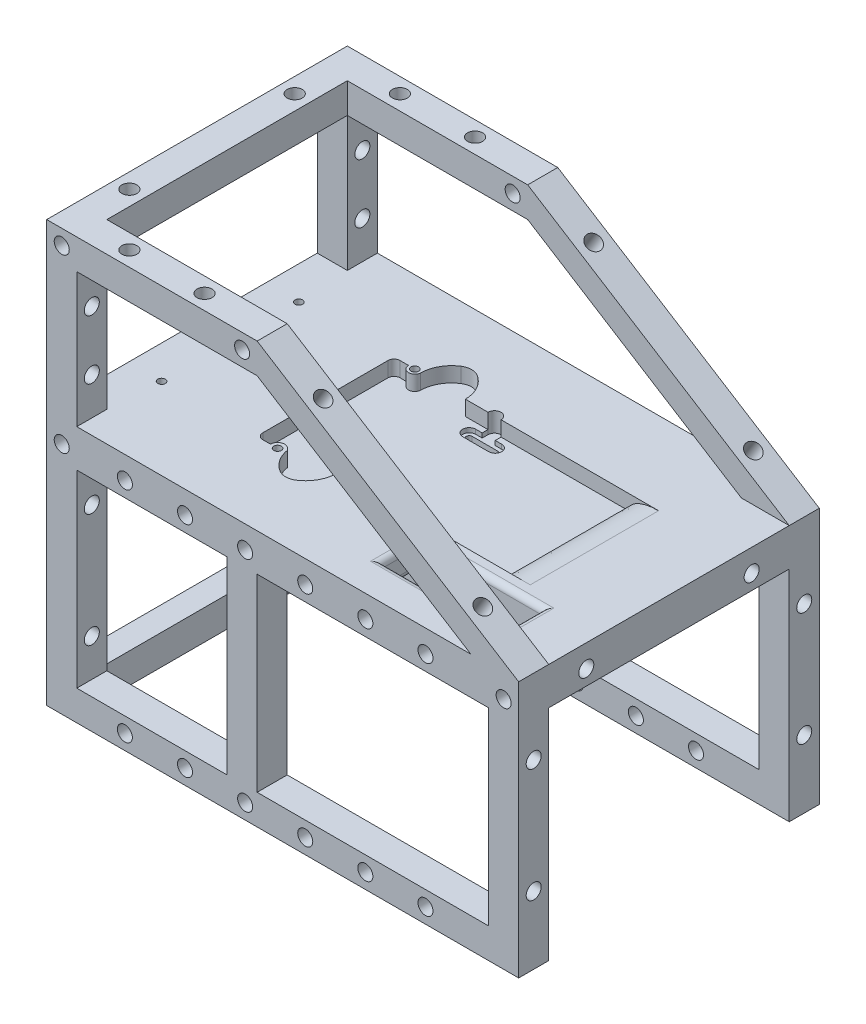
SolidWorks part; units mm, degrees
ref_plane "Front Plane" through (0, 0, 0) normal (0, 0, 1) x (1, 0, 0)
ref_plane "Top Plane" through (0, 0, 0) normal (0, 1, 0) x (1, 0, 0)
ref_plane "Right Plane" through (0, 0, 0) normal (1, 0, 0) x (0, 0, -1)
sketch "Sketch1" plane through (0, 0, 0) normal (0, 1, 0) x (1, 0, 0)
  line L0 (0, 0) -> (0, 50.8)
  line L1 (0, 50.8) -> (50.8, 50.8)
  line L4 (0, 50.8) -> (199.39, 50.8)
  line L5 (0, 50.8) -> (0, 38.1)
  line L8 (0, 50.8) -> (12.7, 50.8)
  line L9 (0, 50.8) -> (0, -76.2)
  line L13 (12.7, -12.7) -> (199.39, -12.7) construction
  line L14 (99.695, 34.925) -> (99.695, -76.2) construction
  line L18 (199.39, 50.8) -> (199.39, -76.2)
  line L19 (199.39, 50.8) -> (186.69, 50.8)
  line L20 (199.39, 50.8) -> (199.39, 38.1)
  line L22 (199.39, 50.8) -> (148.59, 50.8)
  line L23 (199.39, 0) -> (199.39, 50.8)
  line L24 (199.39, -25.4) -> (199.39, -76.2)
  line L25 (199.39, -76.2) -> (148.59, -76.2)
  line L27 (199.39, -76.2) -> (199.39, -63.5)
  line L28 (199.39, -76.2) -> (186.69, -76.2)
  line L29 (0, -76.2) -> (12.7, -76.2)
  line L30 (0, -76.2) -> (0, -63.5)
  line L31 (0, -76.2) -> (199.39, -76.2)
  line L34 (0, -76.2) -> (50.8, -76.2)
  line L35 (0, -25.4) -> (0, -76.2)
  line L36 (12.7, -12.7) -> (12.7, 38.1)
  line L37 (12.7, 38.1) -> (186.69, 38.1)
  line L38 (186.69, 38.1) -> (186.69, -63.5)
  line L39 (186.69, -63.5) -> (12.7, -63.5)
  line L40 (12.7, -63.5) -> (12.7, -12.7)
  point P19 (99.695, 50.8)
  point P22 (99.695, -76.2)
  point P32 (0, -12.7)
  dimension "D1" = 50.8
  dimension "D2" = 50.8
  dimension "D3" = 12.7
  dimension "D4" = 63.5
  dimension "D5" = 12.7
extrude "Boss-Extrude1" add sketch "Sketch1" along normal blind 12.7 contours L38 L39 L40 L36 L37 | L31 L18 L4 L9
sketch "Sketch2" plane through (0, 12.7, 0) normal (0, 1, 0) x (1, 0, 0)
  line L0 (12.7, 38.1) -> (186.69, 38.1) construction
  line L1 (0, 50.8) -> (12.7, 50.8)
  line L2 (0, 50.8) -> (0, 38.1)
  line L3 (0, 38.1) -> (12.7, 38.1)
  line L4 (12.7, 50.8) -> (12.7, 38.1)
  line L5 (199.39, 50.8) -> (186.69, 50.8)
  line L6 (199.39, 50.8) -> (199.39, 38.1)
  line L7 (199.39, 38.1) -> (186.69, 38.1)
  line L8 (186.69, 50.8) -> (186.69, 38.1)
  line L10 (199.39, -76.2) -> (186.69, -76.2)
  line L11 (199.39, -76.2) -> (199.39, -63.5)
  line L12 (199.39, -63.5) -> (186.69, -63.5)
  line L13 (186.69, -76.2) -> (186.69, -63.5)
  line L14 (0, -76.2) -> (12.7, -76.2)
  line L15 (0, -76.2) -> (0, -63.5)
  line L16 (0, -63.5) -> (12.7, -63.5)
  line L17 (12.7, -76.2) -> (12.7, -63.5)
extrude "Boss-Extrude2" add sketch "Sketch2" along normal blind 95.675
sketch "Sketch3" plane through (0, 108.375, 0) normal (0, 1, 0) x (1, 0, 0)
  line L0 (199.39, -76.2) -> (199.39, -63.5) construction
  line L1 (0, 50.8) -> (199.39, 50.8)
  line L2 (0, 50.8) -> (0, -76.2)
  line L3 (0, -76.2) -> (199.39, -76.2)
  line L4 (199.39, 50.8) -> (199.39, -76.2)
  line L5 (186.69, -76.2) -> (199.39, -76.2) construction
  line L7 (12.7, 38.1) -> (186.69, 38.1)
  line L8 (12.7, 38.1) -> (12.7, -63.5)
  line L9 (12.7, -63.5) -> (186.69, -63.5)
  line L10 (186.69, 38.1) -> (186.69, -63.5)
extrude "Boss-Extrude4" add sketch "Sketch3" against normal blind 15.875
sketch "Sketch4" plane through (0, 0, 0) normal (0, -1, 0) x (1, 0, 0)
  line L0 (0, -50.8) -> (199.39, -50.8) construction
  line L1 (0, 76.2) -> (12.7, 76.2)
  line L2 (0, 76.2) -> (0, 63.5)
  line L3 (0, 63.5) -> (12.7, 63.5)
  line L4 (12.7, 76.2) -> (12.7, 63.5)
  line L5 (0, -50.8) -> (12.7, -50.8)
  line L6 (0, -50.8) -> (0, -38.1)
  line L7 (0, -38.1) -> (12.7, -38.1)
  line L8 (12.7, -50.8) -> (12.7, -38.1)
  line L9 (76.2, -50.8) -> (88.9, -50.8)
  line L10 (76.2, -50.8) -> (76.2, -38.1)
  line L11 (76.2, -38.1) -> (88.9, -38.1)
  line L12 (88.9, -50.8) -> (88.9, -38.1)
  line L13 (12.7, -38.1) -> (186.69, -38.1) construction
  line L14 (186.69, 63.5) -> (12.7, 63.5) construction
  line L15 (76.2, 63.5) -> (88.9, 63.5)
  line L16 (76.2, 63.5) -> (76.2, 76.2)
  line L17 (76.2, 76.2) -> (88.9, 76.2)
  line L18 (88.9, 63.5) -> (88.9, 76.2)
  line L19 (0, 76.2) -> (199.39, 76.2) construction
  dimension "D1" = 12.7
  dimension "D2" = 88.9
  dimension "D3" = 88.9
extrude "Boss-Extrude5" add sketch "Sketch4" against normal blind 177.8
sketch "Sketch5" plane through (0, 177.8, 0) normal (0, 1, 0) x (1, 0, 0)
  line L0 (88.9, 50.8) -> (0, 50.8)
  line L1 (0, 50.8) -> (0, -76.2)
  line L2 (0, -76.2) -> (88.9, -76.2)
  line L3 (88.9, -76.2) -> (88.9, -63.5)
  line L4 (88.9, -63.5) -> (12.7, -63.5)
  line L5 (12.7, -63.5) -> (12.7, 38.1)
  line L6 (12.7, 38.1) -> (88.9, 38.1)
  line L7 (88.9, 38.1) -> (88.9, 50.8)
extrude "Boss-Extrude6" add sketch "Sketch5" against normal blind 12.7
sketch "Sketch7" plane through (199.39, 0, 0) normal (1, 0, 0) x (0, 0, -1)
  line L5 (50.8, 0) -> (-76.2, 0) construction
  line L6 (-63.5, 12.7) -> (38.1, 12.7)
  line L7 (-63.5, 12.7) -> (-63.5, 0)
  line L8 (-63.5, 0) -> (38.1, 0)
  line L9 (38.1, 12.7) -> (38.1, 0)
extrude "Cut-Extrude1" cut sketch "Sketch7" against normal blind 15.875
sketch "Sketch8" plane through (12.7, 0, 0) normal (1, 0, 0) x (0, 0, -1)
  line L5 (50.8, 0) -> (38.1, 0) construction
  line L6 (-63.5, 12.7) -> (38.1, 12.7)
  line L7 (-63.5, 12.7) -> (-63.5, 0)
  line L8 (-63.5, 0) -> (38.1, 0)
  line L9 (38.1, 12.7) -> (38.1, 0)
extrude "Cut-Extrude2" cut sketch "Sketch8" against normal blind 2.54
sketch "Sketch9" plane through (0, 0, 76.2) normal (0, 0, 1) x (1, 0, 0)
  line L0 (12.7, 12.7) -> (76.2, 12.7) construction
  line L1 (0, 177.8) -> (0, 0) construction
  line L2 (12.7, 92.5) -> (76.2, 92.5) construction
  circle A0 centre (33.02, 98.85) radius 3.175
  circle A1 centre (58.42, 98.85) radius 3.175
  circle A2 centre (83.82, 98.85) radius 3.175
  circle A3 centre (109.22, 98.85) radius 3.175
  circle A4 centre (134.62, 98.85) radius 3.175
  circle A5 centre (160.02, 98.85) radius 3.175
  circle A6 centre (33.02, 6.35) radius 3.175
  circle A7 centre (58.42, 6.35) radius 3.175
  circle A8 centre (83.82, 6.35) radius 3.175
  circle A9 centre (109.22, 6.35) radius 3.175
  circle A10 centre (134.62, 6.35) radius 3.175
  circle A11 centre (160.02, 6.35) radius 3.175
  dimension "D2" = 6.35
  dimension "D6" = 6.35
  dimension "D1" = 6.35
  dimension "D4" = 33.02
  dimension "D5" = 6.35
  dimension "D3" = 6
  dimension "D7" = 6
extrude "Cut-Extrude3" cut sketch "Sketch9" against normal through all
sketch "Sketch24" plane through (0, 0, 63.5) normal (0, 0, -1) x (-1, 0, 0)
  line L0 (0, 177.8) -> (0, 0) construction
  line L2 (-199.39, 108.375) -> (0, 108.375)
  line L3 (-199.39, 108.375) -> (-199.39, 96.945)
  line L4 (-199.39, 96.945) -> (0, 96.945)
  line L5 (0, 108.375) -> (0, 96.945)
  dimension "D1" = 11.43
extrude "Boss-Extrude8" add sketch "Sketch24" along normal up to surface (101.6 mm away) up to face at (156.845, 98.85, -38.1)
sketch "Sketch10" plane through (0, 0, 76.2) normal (0, 0, 1) x (1, 0, 0)
  line L0 (88.9, 177.8) -> (88.9, 108.375) construction
  line L1 (12.7, 92.5) -> (76.2, 92.5) construction
  line L2 (0, 177.8) -> (0, 0) construction
  line L3 (88.9, 177.8) -> (0, 177.8) construction
  line L4 (199.39, 108.375) -> (199.39, 0) construction
  line L7 (88.9, 92.5) -> (186.69, 92.5) construction
  circle A1 centre (6.35, 98.85) radius 3.175
  circle A2 centre (6.35, 171.45) radius 3.175
  circle A4 centre (82.55, 171.45) radius 3.175
  circle A6 centre (193.04, 98.85) radius 3.175
  dimension "D3" = 6.35
  dimension "D4" = 6.35
  dimension "D5" = 6.35
  dimension "D7" = 6.35
  dimension "D8" = 6.35
  dimension "D10" = 6.35
  dimension "D2" = 6.35
  dimension "D6" = 6.35
  dimension "0." = 6.35
extrude "Cut-Extrude4" cut sketch "Sketch10" against normal blind 15.875
sketch "Sketch11" plane through (0, 0, -50.8) normal (0, 0, -1) x (-1, 0, 0)
  line L0 (-88.9, 177.8) -> (-88.9, 108.375) construction
  line L1 (-199.39, 108.375) -> (-199.39, 0) construction
  line L2 (0, 177.8) -> (0, 0) construction
  line L5 (0, 177.8) -> (-88.9, 177.8) construction
  line L6 (-76.2, 92.5) -> (-12.7, 92.5) construction
  line L7 (-186.69, 92.5) -> (-88.9, 92.5) construction
  circle A3 centre (-6.35, 98.85) radius 3.175
  circle A4 centre (-6.35, 171.45) radius 3.175
  circle A5 centre (-82.55, 171.45) radius 3.175
  circle A6 centre (-193.04, 98.85) radius 3.175
  dimension "D2" = 6.35
  dimension "D3" = 6.35
  dimension "D5" = 6.35
  dimension "D7" = 6.35
  dimension "D8" = 6.35
  dimension "D1" = 6.35
  dimension "D4" = 6.35
  dimension "D6" = 6.35
  dimension "0" = 6.35
extrude "Cut-Extrude5" cut sketch "Sketch11" against normal blind 15.875
sketch "Sketch12" plane through (0, 0, 0) normal (-1, 0, 0) x (0, 0, 1)
  line L0 (-38.1, 92.5) -> (-38.1, 12.7) construction
  line L1 (-38.1, 12.7) -> (63.5, 12.7) construction
  line L2 (-38.1, 92.5) -> (63.5, 92.5) construction
  line L3 (-38.1, 165.1) -> (63.5, 165.1) construction
  line L4 (-38.1, 108.375) -> (63.5, 108.375) construction
  line L5 (12.7, 177.8) -> (12.7, 0) construction
  line L6 (76.2, 177.8) -> (-50.8, 177.8) construction
  line L7 (-50.8, 0) -> (76.2, 0) construction
  line L8 (-44.45, 76.625) -> (-44.45, 28.575) construction
  line L9 (-44.45, 149.225) -> (-44.45, 124.25) construction
  line L10 (-38.1, 165.1) -> (-38.1, 108.375) construction
  circle A0 centre (-44.45, 28.575) radius 3.175
  circle A1 centre (-44.45, 76.625) radius 3.175
  circle A2 centre (-44.45, 124.25) radius 3.175
  circle A3 centre (-44.45, 149.225) radius 3.175
  circle A4 centre (69.85, 149.225) radius 3.175
  circle A5 centre (69.85, 124.25) radius 3.175
  circle A6 centre (69.85, 76.625) radius 3.175
  circle A7 centre (69.85, 28.575) radius 3.175
  dimension "D2" = 6.35
  dimension "D4" = 6.35
  dimension "D6" = 6.35
  dimension "D7" = 6.35
  dimension "D1" = 6.35
  dimension "D3" = 15.875
  dimension "D5" = 15.875
  dimension "D8" = 15.875
  dimension "D9" = 15.875
  dimension "D10" = 6.35
extrude "Cut-Extrude6" cut sketch "Sketch12" against normal blind 15.875
sketch "Sketch15" plane through (0, 0, 0) normal (0, -1, 0) x (1, 0, 0)
  line L0 (10.16, -38.1) -> (199.39, -38.1) construction
  line L1 (199.39, -50.8) -> (199.39, -38.1) construction
  line L3 (0, 76.2) -> (199.39, 76.2) construction
  line L7 (0, -50.8) -> (0, 76.2) construction
  line L8 (0, 12.7) -> (199.39, 12.7) construction
  line L9 (199.39, 63.5) -> (199.39, -38.1) construction
  line L13 (199.39, 63.5) -> (199.39, 76.2) construction
  circle A10 centre (6.35, 69.85) radius 3.175
  circle A11 centre (193.04, 69.85) radius 3.175
  circle A12 centre (6.35, -44.45) radius 3.175
  circle A13 centre (193.04, -44.45) radius 3.175
  dimension "D4" = 6.35
  dimension "D6" = 6.35
  dimension "D7" = 6.35
  dimension "D9" = 0
  dimension "D12" = 6.35
  dimension "D13" = 6.35
  dimension "D2" = 6.35
  dimension "D3" = 6.35
  dimension "D5" = 6.35
  dimension "D8" = 0
  dimension "D10" = 6.35
  dimension "D14" = 6.35
extrude "Cut-Extrude7" cut sketch "Sketch15" against normal blind 15.875
sketch "Sketch16" plane through (0, 177.8, 0) normal (0, 1, 0) x (1, 0, 0)
  line L0 (12.7, 50.8) -> (12.7, 38.1) construction
  line L1 (12.7, 38.1) -> (0, 38.1) construction
  line L2 (76.2, 50.8) -> (76.2, 38.1) construction
  line L3 (0, 50.8) -> (88.9, 50.8) construction
  line L4 (12.7, -63.5) -> (12.7, 38.1) construction
  line L5 (0, -12.7) -> (199.39, -12.7) construction
  line L6 (0, -76.2) -> (0, 50.8) construction
  line L7 (199.39, -76.2) -> (199.39, 50.8) construction
  line L8 (76.2, -76.2) -> (76.2, -63.5) construction
  line L9 (12.7, -63.5) -> (0, -63.5) construction
  line L10 (12.7, -76.2) -> (12.7, -63.5) construction
  line L11 (12.7, -63.5) -> (88.9, -63.5) construction
  circle A0 centre (28.575, 44.45) radius 3.175
  circle A1 centre (60.325, 44.45) radius 3.175
  circle A2 centre (6.35, 22.225) radius 3.175
  circle A3 centre (6.35, -47.625) radius 3.175
  circle A4 centre (60.325, -69.85) radius 3.175
  circle A5 centre (28.575, -69.85) radius 3.175
  dimension "D2" = 6.35
  dimension "D4" = 6.35
  dimension "D5" = 15.875
  dimension "D6" = 6.35
  dimension "D1" = 6.35
  dimension "D3" = 15.875
  dimension "D7" = 15.875
  dimension "D8" = 6.35
  dimension "D9" = 6.35
extrude "Cut-Extrude8" cut sketch "Sketch16" against normal blind 15.875
sketch "Sketch20" plane through (199.39, 0, 0) normal (1, 0, 0) x (0, 0, -1)
  line L0 (-63.5, 92.5) -> (-63.5, 0) construction
  line L1 (38.1, 12.7) -> (-63.5, 12.7) construction
  line L2 (-63.5, 92.5) -> (38.1, 92.5) construction
  line L3 (-76.2, 108.375) -> (-76.2, 0) construction
  line L4 (-63.5, 177.8) -> (-63.5, 108.375) construction
  line L5 (-12.7, 0) -> (-12.7, 177.8) construction
  line L6 (-63.5, 0) -> (38.1, 0) construction
  line L7 (-63.5, 177.8) -> (38.1, 177.8) construction
  circle A0 centre (-69.85, 28.575) radius 3.175
  circle A1 centre (-69.85, 76.625) radius 3.175
  circle A2 centre (-47.625, 98.85) radius 3.175
  circle A3 centre (22.225, 98.85) radius 3.175
  circle A4 centre (44.45, 76.625) radius 3.175
  circle A5 centre (44.45, 28.575) radius 3.175
  dimension "D2" = 6.35
  dimension "D3" = 6.35
  dimension "D5" = 6.35
  dimension "D1" = 6.35
  dimension "0.625" = 15.875
  dimension "D4" = 15.875
  dimension "D6" = 6.35
  dimension "D7" = 15.875
  dimension "D8" = 6.35
extrude "Cut-Extrude11" cut sketch "Sketch20" against normal blind 15.875
sketch "Sketch25" plane through (0, 108.375, 0) normal (0, 1, 0) x (1, 0, 0)
  line L0 (0, 50.8) -> (88.9, 50.8) construction
  line L1 (14.023, -41.7) -> (63.023, -41.7)
  line L2 (14.023, -41.7) -> (14.023, 16.3)
  line L3 (14.023, 16.3) -> (63.023, 16.3)
  line L4 (63.023, -41.7) -> (63.023, 16.3)
  line L5 (14.023, -41.7) -> (63.023, 16.3) construction
  line L6 (14.023, 16.3) -> (63.023, -41.7) construction
  line L7 (0, -76.2) -> (0, 50.8) construction
  line L8 (38.523, -12.7) -> (38.523, 16.3) construction
  line L9 (38.523, -12.7) -> (63.023, -12.7)
  circle A0 centre (63.023, 16.3) radius 1.6
  circle A1 centre (63.023, -41.7) radius 1.6
  circle A2 centre (14.023, -41.7) radius 1.6
  circle A3 centre (14.023, 16.3) radius 1.6
  point P0 (38.523, -12.7)
  dimension "D4" = 38.523
  dimension "D1" = 63.5
  dimension "D2" = 49
  dimension "D3" = 58
extrude "Cut-Extrude12" cut sketch "Sketch25" against normal up to surface (11.43 mm away) contours A2 | A1 | A0 | A3 up to face at (116.5578, 96.945, 12.7)
sketch "Sketch26" plane through (0, 108.375, 0) normal (0, 1, 0) x (1, 0, 0)
  line L0 (63.023, -41.7) -> (63.023, -63.5) construction
  line L5 (12.7, -63.5) -> (88.9, -63.5) construction
  line L6 (126.523, -44.345) -> (177.323, -44.345)
  line L7 (126.523, -44.345) -> (126.523, -60.855)
  line L8 (126.523, -60.855) -> (177.323, -60.855)
  line L9 (177.323, -44.345) -> (177.323, -60.855)
  line L10 (126.523, -44.345) -> (177.323, -60.855) construction
  line L11 (126.523, -60.855) -> (177.323, -44.345) construction
  point P0 (151.923, -52.6)
  point P10 (63.023, -52.6)
  dimension "D1" = 0
  dimension "D2" = 16.51
  dimension "D3" = 50.8
  dimension "D4" = 88.9
extrude "Cut-Extrude13" cut sketch "Sketch26" against normal through all
fillet "Fillet2" radius 2.54 5 edges at (126.523, 96.945, 52.6) (126.523, 108.375, 52.6) (177.323, 108.375, 52.6) (151.923, 108.375, 60.855) (151.923, 108.375, 44.345)
sketch "Sketch28" plane through (12.7, 0, 0) normal (1, 0, 0) x (0, 0, -1)
  line L1 (-63.5, 96.945) -> (38.1, 96.945)
  line L2 (-63.5, 96.945) -> (-63.5, 92.5)
  line L3 (-63.5, 92.5) -> (38.1, 92.5)
  line L4 (38.1, 96.945) -> (38.1, 92.5)
extrude "Cut-Extrude14" cut sketch "Sketch28" against normal blind 6.35
sketch "Sketch29" plane through (0, 0, 76.2) normal (0, 0, 1) x (1, 0, 0)
  line L1 (76.2, 165.1) -> (88.9, 165.1)
  line L2 (76.2, 165.1) -> (76.2, 108.375)
  line L3 (76.2, 108.375) -> (88.9, 108.375)
  line L4 (88.9, 165.1) -> (88.9, 108.375)
extrude "Cut-Extrude15" cut sketch "Sketch29" against normal through all
sketch "Sketch30" plane through (0, 0, 76.2) normal (0, 0, 1) x (1, 0, 0)
  line L0 (88.9, 177.8) -> (199.39, 108.375)
  line L1 (199.39, 108.375) -> (199.39, 0) construction
  line L2 (12.7, 108.375) -> (199.39, 108.375) construction
  line L3 (88.9, 165.1) -> (179.1779, 108.375)
  line L4 (179.1779, 108.375) -> (199.39, 108.375)
  line L5 (88.9, 177.8) -> (88.9, 165.1)
extrude "Boss-Extrude9" add sketch "Sketch30" against normal up to surface (12.7 mm away) contours L3 L4 L0 L5 up to face at (85.725, 171.45, 63.5)
sketch "Sketch31" plane through (0, 0, -50.8) normal (0, 0, -1) x (-1, 0, 0)
  line L0 (-88.9, 177.8) -> (-88.9, 165.1)
  line L1 (-88.9, 177.8) -> (-199.39, 108.375)
  line L2 (-88.9, 165.1) -> (-179.1779, 108.375)
  line L3 (-179.1779, 108.375) -> (-199.39, 108.375)
extrude "Boss-Extrude10" add sketch "Sketch31" against normal up to surface (12.7 mm away) up to face at (79.375, 171.45, -38.1)
sketch "Sketch32" plane through (105.2595, 167.5207, 0) normal (0.532, 0.8467, 0) x (0.8467, -0.532, 0)
  line L0 (-19.3209, 50.8) -> (111.17, 50.8) construction
  line L1 (-19.3209, 50.8) -> (-19.3209, 38.1) construction
  line L3 (111.17, 38.1) -> (111.17, 50.8) construction
  line L4 (111.17, -12.7) -> (-94.5948, -12.7) construction
  line L5 (111.17, -63.5) -> (111.17, 38.1) construction
  line L6 (-94.5948, -76.2) -> (-94.5948, 50.8) construction
  circle A0 centre (6.0791, 44.45) radius 3.175
  circle A1 centre (85.77, 44.45) radius 3.175
  circle A2 centre (85.77, -69.85) radius 3.175
  circle A3 centre (6.0791, -69.85) radius 3.175
  dimension "D1" = 6.35
  dimension "D2" = 6.35
  dimension "D3" = 6.35
  dimension "D4" = 6.35
  dimension "D5" = 25.4
  dimension "D6" = 25.4
extrude "Cut-Extrude16" cut sketch "Sketch32" against normal blind 12.7
sketch "Sketch34" plane through (0, 108.375, 0) normal (0, 1, 0) x (1, 0, 0)
  line L0 (63.023, 16.3) -> (63.023, -41.7) construction
  line L1 (153.663, -38.3) -> (65.663, -38.3)
  line L5 (153.663, 15.95) -> (153.663, -38.3)
  line L6 (65.663, -38.3) -> (65.663, 15.95)
  line L7 (65.663, 15.95) -> (153.663, 15.95)
  dimension "D1" = 88
  dimension "D2" = 5.28
  dimension "D3" = 54.25
extrude "Cut-Extrude18" cut sketch "Sketch34" against normal blind 6.35
sketch "Sketch35" plane through (0, 108.375, 0) normal (0, 1, 0) x (1, 0, 0)
  line L0 (65.663, 15.95) -> (84.713, 15.95)
  line L1 (153.663, 15.95) -> (65.663, 15.95) construction
  line L2 (65.663, -11.175) -> (153.663, -11.175) construction
  line L3 (65.663, -38.3) -> (84.713, -38.3)
  line L4 (65.663, -38.3) -> (153.663, -38.3) construction
  line L5 (75.188, 15.95) -> (75.188, 28.65) construction
  arc A0 (65.663, 15.95) -> (71.7688, 27.0976) centre (78.8922, 15.95) cw
  arc A2 (84.713, 15.95) -> (78.6072, 27.0976) centre (71.4838, 15.95) ccw
  arc A3 (78.6072, 27.0976) -> (71.7688, 27.0976) centre (75.188, 21.7467) ccw
  arc A4 (78.6072, -49.4476) -> (71.7688, -49.4476) centre (75.188, -44.0967) cw
  arc A5 (84.713, -38.3) -> (78.6072, -49.4476) centre (71.4838, -38.3) cw
  arc A6 (65.663, -38.3) -> (71.7688, -49.4476) centre (78.8922, -38.3) ccw
  dimension "D4" = 6.35
  dimension "D1" = 19.05
  dimension "D2" = 12.7
  dimension "D3" = 0
extrude "Cut-Extrude19" cut sketch "Sketch35" against normal blind 6.35
fillet "Fillet3" radius 12.7 1 edges at (153.663, 108.375, 11.175) second distance 6.35 first distance on face at (90.883, 108.375, 11.175)
ref_plane "Plane1" through (0, 115.8745, 0) normal (0, 1, 0) x (1, 0, 0)
sketch "Sketch37" plane through (0, 108.375, 0) normal (0, 1, 0) x (1, 0, 0)
  line L0 (65.663, -38.3) -> (97.033, -38.3)
  line L1 (84.713, -38.3) -> (153.663, -38.3) construction
  line L2 (97.033, -38.3) -> (97.033, -35.25)
  dimension "D1" = 31.37
  dimension "D2" = 3.05
sketch "Sketch38" plane through (0, 108.375, 0) normal (0, 1, 0) x (1, 0, 0)
  line L0 (89.533, -35.25) -> (104.533, -35.25)
  line L1 (89.533, -35.25) -> (89.533, -30.25)
  line L2 (89.533, -30.25) -> (104.533, -30.25)
  line L3 (104.533, -30.25) -> (104.533, -35.25)
  line L4 (91.533, -32) -> (102.533, -32)
  line L5 (91.533, -34.5) -> (102.533, -34.5)
  line L9 (91.533, 12) -> (102.533, 12)
  line L10 (91.533, 9.5) -> (102.533, 9.5)
  line L11 (91.533, -33.25) -> (91.533, 10.75) construction
  arc A0 (91.533, -32) -> (91.533, -34.5) centre (91.533, -33.25) ccw
  arc A1 (102.533, -34.5) -> (102.533, -32) centre (102.533, -33.25) ccw
  arc A2 (102.533, 12) -> (102.533, 9.5) centre (102.533, 10.75) cw
  arc A3 (91.533, 9.5) -> (91.533, 12) centre (91.533, 10.75) cw
  point P4 (97.033, -35.25)
  dimension "D3" = 2
  dimension "2.5mm" = 2.5
  dimension "D5" = 2.5
  dimension "D1" = 15
  dimension "D2" = 5
  dimension "D4" = 2
  dimension "D6" = 2
  dimension "D7" = 2
  dimension "D8" = 44
extrude "Cut-Extrude20" cut sketch "Sketch38" against normal through all and the other way through all contours L4 A1 L5 A0 | A3 L9 A2 L10
sketch "Sketch41" plane through (0, 102.025, 0) normal (0, 1, 0) x (1, 0, 0)
  line L2 (91.533, 10.75) -> (102.533, 10.75) construction
  line L3 (91.533, -30.5) -> (102.533, -30.5)
  line L6 (91.533, -36) -> (102.533, -36)
  line L7 (91.533, 13.5) -> (102.533, 13.5)
  line L9 (91.533, 8) -> (102.533, 8)
  arc A4 (102.533, 13.5) -> (102.533, 8) centre (102.533, 10.75) cw
  arc A5 (91.533, 8) -> (91.533, 13.5) centre (91.533, 10.75) cw
  arc A7 (91.533, -30.5) -> (91.533, -36) centre (91.533, -33.25) ccw
  arc A8 (102.533, -36) -> (102.533, -30.5) centre (102.533, -33.25) ccw
  arc A9 (91.533, 12) -> (91.533, 9.5) centre (91.533, 10.75) ccw construction
  point P17 (90.283, 10.75)
  dimension "D1" = 5.5
  dimension "D2" = 5.5
  dimension "D3" = 0
extrude "Cut-Extrude21" cut sketch "Sketch41" against normal blind 1.878
sketch "Sketch42" plane through (0, 108.375, 0) normal (0, 1, 0) x (1, 0, 0)
  line L0 (65.663, -11.175) -> (166.363, -11.175) construction
  line L1 (65.663, 15.95) -> (65.663, -38.3) construction
  line L2 (84.713, -38.3) -> (166.363, -38.3) construction
  line L3 (94.283, -38.3) -> (94.283, -36)
  line L4 (91.533, -36) -> (102.533, -36) construction
  line L5 (94.283, -36) -> (99.783, -36)
  line L6 (91.533, -36) -> (102.533, -36) construction
  line L7 (99.783, -36) -> (99.783, -38.3)
  line L8 (166.363, 15.95) -> (166.363, -38.3) construction
  line L9 (99.783, 13.65) -> (99.783, 15.95)
  line L11 (94.283, 15.95) -> (94.283, 13.65)
  line L12 (94.283, 13.65) -> (94.283, 13.5)
  line L13 (102.533, 13.5) -> (91.533, 13.5) construction
  line L14 (94.283, 13.5) -> (99.783, 13.5)
  line L15 (99.783, 13.5) -> (99.783, 13.65)
  arc A0 (94.283, -38.3) -> (99.783, -38.3) centre (97.033, -38.3) ccw
  arc A1 (94.283, 15.95) -> (99.783, 15.95) centre (97.033, 15.95) cw
  dimension "D1" = 5.5
  dimension "D2" = 0
extrude "Cut-Extrude22" cut sketch "Sketch42" against normal up to surface (8.228 mm away) up to face at (97.033, 100.147, -10.75)
sketch "Sketch43" plane through (0, 96.945, 0) normal (0, -1, 0) x (1, 0, 0)
  circle A0 centre (63.023, 41.7) radius 2.54
  circle A1 centre (63.023, -16.3) radius 2.54
  circle A2 centre (14.023, -16.3) radius 2.54
  circle A3 centre (14.023, 41.7) radius 2.54
  dimension "D1" = 5.08
  dimension "D2" = 5.08
  dimension "D3" = 5.08
  dimension "D4" = 5.08
extrude "Cut-Extrude23" cut sketch "Sketch43" against normal blind 8.255
sketch "Sketch44" plane through (0, 0, 76.2) normal (0, 0, 1) x (1, 0, 0)
  line L0 (0, 177.8) -> (138.1279, 177.8) construction
  line L1 (88.9, 177.8) -> (199.39, 108.375) construction
  line L2 (199.39, 108.375) -> (151.2695, 108.375) construction
  dimension "D1" = 32.143
  dimension "D2" = 32.143
sketch "Sketch45" plane through (0, 108.375, 0) normal (0, 1, 0) x (1, 0, 0)
  line L0 (60.0229, -41.7) -> (60.0231, -41.6651)
  line L2 (65.663, 15.95) -> (65.663, -38.3)
  line L3 (65.663, 15.95) -> (65.663, -38.3)
  line L4 (60.3599, 16.3) -> (56.773, 16.3)
  line L5 (65.663, -38.3) -> (65.9075, -40.2748)
  line L6 (65.9075, -40.2748) -> (65.663, -40.2748)
  line L7 (54.233, 13.76) -> (54.233, -39.1447)
  line L8 (56.7883, -41.6846) -> (60.0231, -41.6651)
  line L9 (63.023, 16.3) -> (62.8476, 13.6427) construction
  arc A0 (60.3599, 16.3) -> (65.663, 15.95) centre (63.023, 16.3) ccw
  arc A1 (60.0231, -41.6651) -> (60.0229, -41.7) centre (63.023, -41.7) ccw
  arc A2 (65.663, -40.2748) -> (60.0229, -41.7) centre (63.023, -41.7) ccw
  arc A3 (54.233, -39.1447) -> (56.7883, -41.6846) centre (56.773, -39.1447) ccw
  arc A4 (56.773, 16.3) -> (54.233, 13.76) centre (56.773, 13.76) ccw
  arc M5 (71.7688, -49.4476) -> (65.663, -38.3) centre (78.8922, -38.3) cw
  line M6 (65.663, -38.3) -> (65.663, 15.95)
  dimension "D2" = 2.54
  dimension "D1" = 11.43
  dimension "D3" = 2.6631
extrude "Cut-Extrude25" cut sketch "Sketch45" against normal up to surface (6.35 mm away) contours A2 L6 A0 L0 M5 M6 region at (59.8527, 108.375, 12.5856) up to face at (94.6676, 102.025, 12.2529)
sketch "Sketch46" plane through (199.39, 0, 0) normal (1, 0, 0) x (0, 0, -1)
  line L0 (-63.5, 0) -> (-63.5, 92.5)
  line L1 (-76.2, 0) -> (-63.5, 0)
  line L2 (-76.2, 0) -> (-76.2, 108.375)
  line L3 (-76.2, 108.375) -> (50.8, 108.375)
  line L4 (50.8, 0) -> (50.8, 108.375)
  line L5 (-63.5, 92.5) -> (38.1, 92.5)
  line L6 (38.1, 92.5) -> (38.1, 0)
  line L7 (38.1, 0) -> (50.8, 0)
  line L8 (38.1, 12.7) -> (-63.5, 12.7) construction
  circle A0 centre (-69.85, 28.575) radius 3.175
  circle A1 centre (-69.85, 76.625) radius 3.175
  circle A2 centre (-47.625, 98.85) radius 3.175
  dimension "D11" = 6.35
  dimension "D1" = 108.375
  dimension "D2" = 12.7
  dimension "D3" = 15.875
  dimension "D4" = 92.5
  dimension "D5" = 127
  dimension "D6" = 15.875
  dimension "D7" = 15.875
  dimension "D8" = 15.875
  dimension "D9" = 6.35
  dimension "D10" = 12.7
